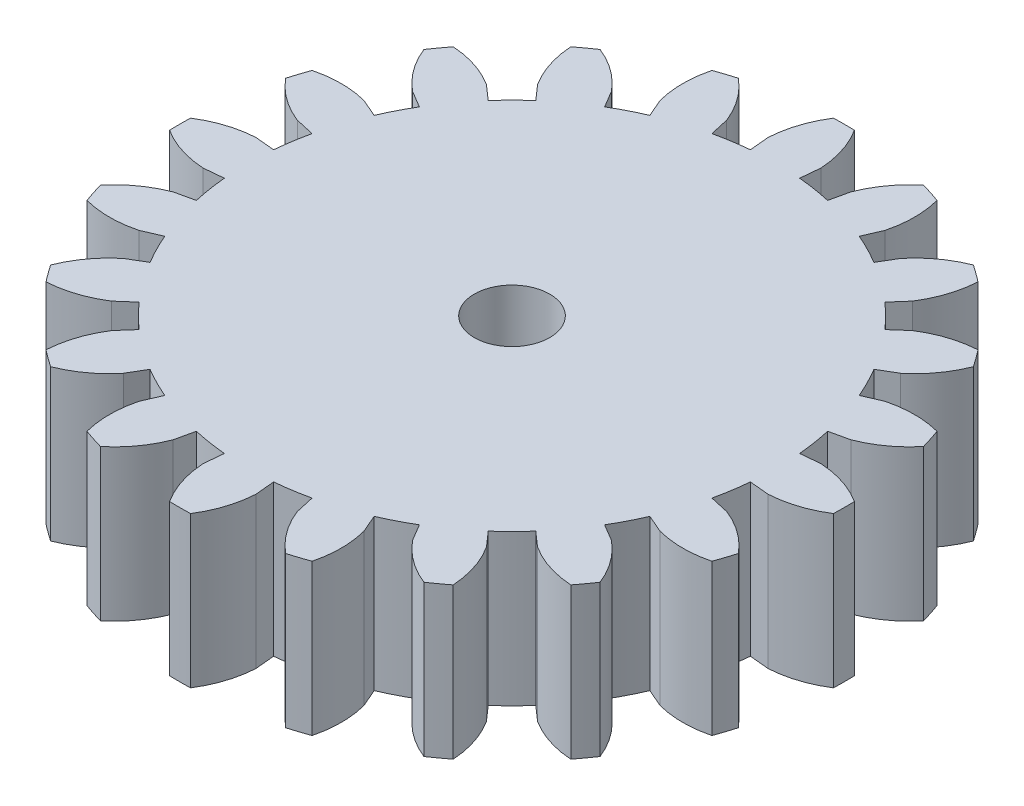
SolidWorks part; units mm, degrees
ref_plane "Спереди" through (0, 0, 0) normal (0, 0, 1) x (1, 0, 0)
ref_plane "Сверху" through (0, 0, 0) normal (0, 1, 0) x (1, 0, 0)
ref_plane "Справа" through (0, 0, 0) normal (1, 0, 0) x (0, 0, -1)
other "Configuration Table"
sketch "Эскиз1" plane through (0, 0, 0) normal (0, 1, 0) x (1, 0, 0)
  circle A0 centre (0, 0) radius 17.5
  dimension "D1" = 35
extrude "Бобышка-Вытянуть1" add sketch "Эскиз1" along normal blind 10
sketch "Эскиз2" plane through (0, 0, 0) normal (0, -1, 0) x (1, 0, 0)
  line L0 (0, 0) -> (0, 22) construction
  line L1 (0, 0) -> (-1.7523, 18.712) construction
  line L2 (0, 0) -> (1.7523, 18.712) construction
  line L5 (-1.5692, 19.9383) -> (0, 0) construction
  line L6 (0, 0) -> (1.5692, 19.9383) construction
  line L7 (-0.6949, 21.989) -> (0, 0) construction
  line L8 (-1.6317, 17.4238) -> (-1.7523, 18.712)
  line L9 (1.7523, 18.712) -> (1.6317, 17.4238)
  circle A0 centre (0, 0) radius 18.7938 construction
  circle A1 centre (0, 0) radius 20 construction
  circle A2 centre (0, 0) radius 22 construction
  arc A3 (-0.6949, 21.989) -> (0.6949, 21.989) centre (0, 0) cw
  arc A4 (-1.6317, 17.4238) -> (1.6317, 17.4238) centre (0, 0) cw
  circle A5 centre (0, 0) radius 17.5 construction
  arc A6 (-1.5692, 19.9383) -> (1.5692, 19.9383) centre (0, 0) cw construction
  arc A7 (-1.7523, 18.712) -> (-0.6949, 21.989) centre (5.0681, 18.3203) cw
  arc A8 (0.6949, 21.989) -> (1.7523, 18.712) centre (-5.0681, 18.3203) cw
  point P12 (0, 20)
  point P16 (0, 22)
  point P22 (0, 17.5)
  dimension "D1" = 37.5877
  dimension "D2" = 40
  dimension "D3" = 44
  dimension "D4" = 5.35
  dimension "D5" = 4.5
  dimension "D6" = 1.81
extrude "Бобышка-Вытянуть2" add sketch "Эскиз2" against normal blind 10
pattern_circular "Круговой массив1" count 20 over 360 about axis through (0, 10, 0) along (0, -1, 0) of "Бобышка-Вытянуть2" reverse direction yes
sketch "Эскиз3" plane through (0, 0, 0) normal (0, -1, 0) x (1, 0, 0)
  circle A0 centre (0, 0) radius 2.5
  dimension "D1" = 5
extrude "Вырез-Вытянуть1" cut sketch "Эскиз3" against normal through all
equation "\"Ширина груза\"= 420"
equation "\"Глубина груза\"= 490"
equation "\"Высота груза\"= 297"
equation "\"Ширина ячейки\"= \"Ширина груза\" + 10"
equation "\"Глубина ячейки\"= \"Глубина груза\" + 10"
equation "\"Высота ячейки\"= \"Высота груза\" + 10 + 13"
equation "\"Колво ячеек ширина\"= 2"
equation "\"Колво ячеек высота\"= 2"
equation "\"Толщина стенки\" = 6"
equation "\"Крепление дверцы\"= 5 "
equation "\"Ширина рейки\"= \"Толщина шестерни\""
equation "\"Высота рейки\"= 20"
equation "\"Высота пола\"= \"Толщина стенки\" * 2"
equation "\"Колво полозьев\"= 5"
equation "\"Отступ рейки\"= 20"
equation "\"Глубина каретки\"= \"Глубина ячейки\" + 30 + \"Мотор Y высота корпуса\" + 20"
equation "\"Длинна рейки\"= ( \"Ширина ячейки\" + \"Толщина стенки\" + \"Крепление дверцы\" ) * \"Колво ячеек ширина\" + \"Ширина ячейки выгрузки\" * \"Колво выгрузки\" + \"Толщина стенки\""
equation "\"Отступ шпильки\"= 26"
equation "\"Диаметр шпильки\"= 5"
equation "\"Длинна шпильки\"= ( \"Высота ячейки\" + \"Толщина стенки\" + \"Высота пола\" ) * \"Колво ячеек высота\" + ( \"Толщина стенки\" + \"Отступ рейки\" ) * 2 "
equation "\"Ширина пластины\"= 50  "
equation "\"Высота зона выгрузки\"= \"Высота ячейки\" * 2 + \"Толщина стенки\" * 2"
equation "\"Колво выгрузки\"= 1"
equation "\"Ширина ячейки выгрузки\"= \"Ширина ячейки\" + \"Толщина стенки\" + \"Отступ крепления мотора фиксации\"*2"
equation "\"Отступ крепления мотора фиксации\" = 30"
equation "\"Мотор X ширина корпуса\"= 42.3"
equation "\"Мотор X высота корпуса\"= 42.3"
equation "\"Мотор X длина корпуса\"= 40"
equation "\"Мотор X вылет вала\"= 19.8"
equation "\"Мотор Y ширина корпуса\"= 42.3"
equation "\"Мотор Y высота корпуса\"= 42.3"
equation "\"Мотор Y длина корпуса\"= 48"
equation "\"Мотор Y вылет вала\"= 30"
equation "\"Мотор Z ширина корпуса\"= 42"
equation "\"Мотор Z высота корпуса\"= 42"
equation "\"Мотор Z длина корпуса\"= 40"
equation "\"Мотор Z вылет вала\"= 23"
equation "\"Мотор диаметр вала ПРЕДВ\"= 5"
equation "\"Мотор шаг крепления ПРЕДВ\"= 31"
equation "\"Мотор диаметр отверстий ПРЕДВ\"= 3"
equation "\"Мотор глубина отверстий ПРЕДВ\"= 4.5"
equation "\"Мотор диаметр буртика ПРЕДВ\"= 22"
equation "\"Мотор высота буртика ПРЕДВ\"= 2"
equation "\"Мотор диаметр шкива ПРЕДВ\"= 16"
equation "\"Мотор длина шкива ПРЕДВ\"= 12"
equation "\"Мотор отступ шкива ПРЕДВ\"= 5"
equation "\"Мотор X шаг градусов\"= 1.8"
equation "\"Мотор Y шаг градусов\"= 1.8"
equation "\"Мотор Z шаг градусов\"= 1.8"
equation "\"Мотор Y диаметр ротора\"= 25.78"
equation "\"Толщина шестерни\"= 10"
equation "\"D1@Бобышка-Вытянуть1\"=\"Толщина шестерни\""
equation "\"D1@Бобышка-Вытянуть2\"=\"Толщина шестерни\""
equation "\"D1@Эскиз3\"=\"Мотор диаметр вала ПРЕДВ\""
